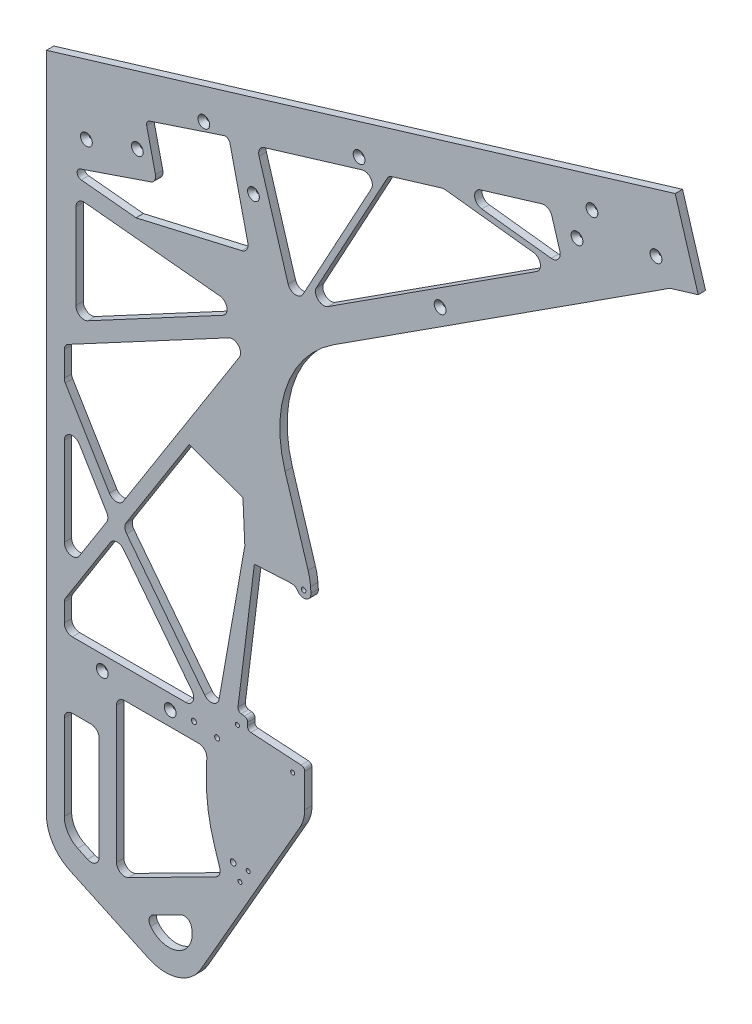
SolidWorks part; units mm, degrees
material "Beech"
ref_plane "Front Plane" through (0, 0, 0) normal (0, 0, 1) x (1, 0, 0)
ref_plane "Top Plane" through (0, 0, 0) normal (0, 1, 0) x (1, 0, 0)
ref_plane "Right Plane" through (0, 0, 0) normal (1, 0, 0) x (0, 0, -1)
sketch "Sketch1" plane through (0, 0, 0) normal (0, 0, 1) x (1, 0, 0)
  line L3 (-17.0528, -329.4943) -> (-52.061, -347.2658)
  line L9 (-123, -235.7894) -> (-123, -309.0696)
  line L10 (-100, -228.7894) -> (-116, -228.7894)
  line L11 (-93, -324.8124) -> (-93, -235.7894)
  line L12 (-111.4524, -327.1958) -> (-102.9583, -331.1566)
  line L20 (84, -200.7842) -> (84, -172.0664)
  line L21 (81.0197, -168.8973) -> (37.7062, -166.2368)
  line L23 (81.0197, -168.8973) -> (37.7062, -166.2368)
  line L24 (89.4313, -36.4853) -> (89.0709, -31.7487)
  line L25 (86.9733, -20.7388) -> (67.1502, 43.2142)
  line L39 (109.0999, 158.659) -> (398.6241, 345.5216)
  line L40 (398.6241, 345.5216) -> (422.935, 352.8794)
  line L46 (422.935, 352.8794) -> (403.0991, 418.4193)
  line L47 (403.0991, 418.4193) -> (-138.3789, 254.5381)
  line L48 (-138.3789, 254.5381) -> (-138.3789, -315.4534)
  line L49 (-118.2139, -347.1062) -> (-50.5059, -378.6789)
  line L50 (-5.4671, -364.4315) -> (80.009, -215.7351)
  line L55 (84, -200.7842) -> (84, -172.0664)
  line L62 (89.4313, -36.4853) -> (89.0709, -31.7487)
  line L63 (86.9733, -20.7388) -> (67.1502, 43.2142)
  line L64 (109.0999, 158.659) -> (398.6241, 345.5216)
  line L65 (398.6241, 345.5216) -> (422.935, 352.8794)
  line L66 (422.935, 352.8794) -> (403.0991, 418.4193)
  line L67 (403.0991, 418.4193) -> (-138.3789, 254.5381)
  line L68 (-138.3789, 254.5381) -> (-138.3789, -315.4534)
  line L69 (-61.1998, 168.1794) -> (29.8266, 189.1945)
  line L70 (-108.3476, 172.8251) -> (-61.1998, 168.1794)
  line L71 (-43.1791, 203.129) -> (-109.2468, 180.5917)
  line L72 (-52.0322, 241.4762) -> (-43.1791, 203.129)
  line L73 (14.4833, 267.3378) -> (-49.3928, 246.173)
  line L74 (35.0726, 197.5898) -> (19.6388, 264.4406)
  line L75 (-102.6958, 70.6213) -> (13.5473, 132.8622)
  line L76 (-113, 150.4873) -> (-113, 76.7923)
  line L77 (10.9295, 145.9995) -> (-105.3136, 157.4535)
  line L78 (-118.2139, -347.1062) -> (-50.5059, -378.6789)
  line L79 (-5.4671, -364.4315) -> (80.009, -215.7351)
  line L81 (-123, -28.6549) -> (-123, -104.7468)
  line L82 (-86.4916, -64.103) -> (-110.0027, -25.0448)
  line L83 (-110.0903, -108.4986) -> (-86.5792, -71.4649)
  line L91 (-78, -203.7894) -> (-78, -320.9929)
  line L92 (-7.2478, -196.7894) -> (-71, -196.7894)
  line L93 (-0.5975, -217.2122) -> (-0.2502, -203.9729)
  line L94 (10.9062, -280.6638) -> (6.4944, -266.8845)
  line L95 (-67.8314, -327.2347) -> (7.4081, -289.0401)
  line L97 (43.2335, -2.4917) -> (44.321, -25.8402) construction
  line L98 (69.3512, -23.7337) -> (62.886, 0.5467) construction
  line L99 (47.5047, -28.6948) -> (66.6392, -27.4998) construction
  line L107 (-15.4708, 21.8839) -> (-69.6883, -63.5168)
  line L108 (30.8453, 5.5646) -> (-15.4708, 21.8839)
  line L109 (32.4846, -29.6329) -> (30.8453, 5.5646)
  line L110 (10.3168, -155.1041) -> (32.4846, -29.6329)
  line L111 (-69.3092, -71.5595) -> (-2.1071, -158.1772)
  line L115 (-83.3585, -85.0495) -> (-123, -147.491)
  line L116 (-12.9629, -160.4984) -> (-71.9182, -84.5103)
  line L117 (-116, -171.7894) -> (-18.4936, -171.7894)
  line L118 (-123, -147.491) -> (-123, -164.7894)
  line L123 (18.5117, 118.5054) -> (-123, 42.7347)
  line L124 (-72.2002, -48.8158) -> (27.7256, 108.5825)
  line L125 (-123, 15.9373) -> (-84.1071, -48.674)
  line L126 (-123, 42.7347) -> (-123, 15.9373)
  line L166 (26.578, -152.854) -> (40.7015, -39.1783)
  line L183 (26.578, -152.854) -> (40.7015, -39.1783)
  line L184 (40.7015, -39.1783) -> (72.3075, -37.5674)
  line L185 (40.7015, -39.1783) -> (72.3075, -37.5674)
  line L240 (34.7318, -162.8731) -> (34.9029, -160.088)
  line L241 (34.7318, -162.8731) -> (34.9029, -160.088)
  line L242 (32.1253, -156.7426) -> (29.3373, -156.3962)
  line L243 (32.1253, -156.7426) -> (29.3373, -156.3962)
  circle A2 centre (83.098, -37.255) radius 2
  arc A4 (-52.061, -347.2658) -> (-17.0528, -329.4943) centre (-32.8243, -341.7931) ccw
  arc A20 (-123, -309.0696) -> (-111.4524, -327.1958) centre (-103, -309.0696) ccw
  arc A21 (-116, -228.7894) -> (-123, -235.7894) centre (-116, -235.7894) ccw
  arc A22 (-93, -235.7894) -> (-100, -228.7894) centre (-100, -235.7894) ccw
  arc A23 (-102.9583, -331.1566) -> (-93, -324.8124) centre (-100, -324.8124) ccw
  arc A31 (89.0709, -31.7487) -> (86.9733, -20.7388) centre (39.215, -35.5422) ccw
  arc A34 (109.0999, 158.659) -> (67.1502, 43.2142) centre (164.1952, 73.2946) ccw
  arc A35 (-138.3789, -315.4534) -> (-118.2139, -347.1062) centre (-103.4539, -315.4534) ccw
  arc A36 (-50.5059, -378.6789) -> (-5.4671, -364.4315) centre (-35.746, -347.0261) ccw
  arc A37 (80.009, -215.7351) -> (84, -200.7842) centre (54, -200.7842) ccw
  arc A46 (29.8266, 189.1945) -> (35.0726, 197.5898) centre (28.252, 196.0151) ccw
  arc A47 (-109.2468, 180.5917) -> (-108.3476, 172.8251) centre (-107.9554, 176.8059) ccw
  arc A48 (-49.3928, 246.173) -> (-52.0322, 241.4762) centre (-48.1347, 242.376) ccw
  arc A49 (19.6388, 264.4406) -> (14.4833, 267.3378) centre (15.7414, 263.5408) ccw
  arc A50 (89.0709, -31.7487) -> (86.9733, -20.7388) centre (39.215, -35.5422) ccw
  arc A51 (109.0999, 158.659) -> (67.1502, 43.2142) centre (164.1952, 73.2946) ccw
  arc A52 (13.5473, 132.8622) -> (10.9295, 145.9995) centre (10.2431, 139.0332) ccw
  arc A53 (-113, 76.7923) -> (-102.6958, 70.6213) centre (-106, 76.7923) ccw
  arc A54 (-105.3136, 157.4535) -> (-113, 150.4873) centre (-106, 150.4873) ccw
  arc A55 (-138.3789, -315.4534) -> (-118.2139, -347.1062) centre (-103.4539, -315.4534) ccw
  arc A56 (-50.5059, -378.6789) -> (-5.4671, -364.4315) centre (-35.746, -347.0261) ccw
  arc A57 (80.009, -215.7351) -> (84, -200.7842) centre (54, -200.7842) ccw
  arc A58 (-110.0027, -25.0448) -> (-123, -28.6549) centre (-116, -28.6549) ccw
  arc A59 (-86.5792, -71.4649) -> (-86.4916, -64.103) centre (-92.4888, -67.7131) ccw
  arc A60 (-123, -104.7468) -> (-110.0903, -108.4986) centre (-116, -104.7468) ccw
  arc A68 (-78, -320.9929) -> (-67.8314, -327.2347) centre (-71, -320.9929) ccw
  arc A69 (-71, -196.7894) -> (-78, -203.7894) centre (-71, -203.7894) ccw
  arc A70 (-0.2502, -203.9729) -> (-7.2478, -196.7894) centre (-7.2478, -203.7894) ccw
  arc A71 (-0.5975, -217.2122) -> (6.4944, -266.8845) centre (149.3509, -221.1459) ccw
  arc A72 (7.4081, -289.0401) -> (10.9062, -280.6638) centre (4.2395, -282.7983) ccw
  arc A74 (44.321, -25.8402) -> (47.5047, -28.6948) centre (47.3177, -25.7007) ccw construction
  arc A75 (62.886, 0.5467) -> (43.2335, -2.4917) centre (53.2227, -2.0264) ccw construction
  arc A76 (66.6392, -27.4998) -> (69.3512, -23.7337) centre (66.4522, -24.5056) ccw construction
  arc A78 (-69.6883, -63.5168) -> (-69.3092, -71.5595) centre (-63.7786, -67.2686) ccw
  arc A79 (-2.1071, -158.1772) -> (10.3168, -155.1041) centre (3.4235, -153.8863) ccw
  arc A84 (-71.9182, -84.5103) -> (-83.3585, -85.0495) centre (-77.4488, -88.8013) ccw
  arc A85 (-18.4936, -171.7894) -> (-12.9629, -160.4984) centre (-18.4936, -164.7894) ccw
  arc A86 (-123, -164.7894) -> (-116, -171.7894) centre (-116, -164.7894) ccw
  arc A88 (27.7256, 108.5825) -> (18.5117, 118.5054) centre (21.8159, 112.3343) ccw
  arc A89 (-84.1071, -48.674) -> (-72.2002, -48.8158) centre (-78.1098, -45.064) ccw
  arc A122 (84, -172.0664) -> (81.0197, -168.8973) centre (80.825, -172.0664) ccw
  arc A123 (84, -172.0664) -> (81.0197, -168.8973) centre (80.825, -172.0664) ccw
  arc A126 (77.9448, -40.4332) -> (83.5751, -43.2993) centre (83.2589, -36.9572) ccw
  arc A127 (77.9448, -40.4332) -> (83.5751, -43.2993) centre (83.2589, -36.9572) ccw
  arc A128 (83.5751, -43.2993) -> (89.4313, -36.4853) centre (83.0996, -36.9671) ccw
  arc A129 (83.5751, -43.2993) -> (89.4313, -36.4853) centre (83.0996, -36.9671) ccw
  arc A136 (77.9448, -40.4332) -> (72.3075, -37.5674) centre (72.6307, -43.9092) ccw
  arc A137 (77.9448, -40.4332) -> (72.3075, -37.5674) centre (72.6307, -43.9092) ccw
  arc A162 (34.7318, -162.8731) -> (37.7062, -166.2368) centre (37.9008, -163.0678) ccw
  arc A163 (34.7318, -162.8731) -> (37.7062, -166.2368) centre (37.9008, -163.0678) ccw
  arc A164 (34.9029, -160.088) -> (32.1253, -156.7426) centre (31.7338, -159.8934) ccw
  arc A165 (34.9029, -160.088) -> (32.1253, -156.7426) centre (31.7338, -159.8934) ccw
  arc A166 (26.578, -152.854) -> (29.3373, -156.3962) centre (29.7288, -153.2454) ccw
  arc A167 (26.578, -152.854) -> (29.3373, -156.3962) centre (29.7288, -153.2454) ccw
  line B0 (236.5506, 323.6498) -> (296.3216, 316.7428)
  line B1 (288.1657, 353.2968) -> (235.3263, 337.3033)
  line B2 (303.8249, 325.7244) -> (296.8934, 348.6248)
  line B3 (104.1239, 184.6459) -> (283.8662, 300.6596)
  line B4 (156.4343, 308.2003) -> (94.1802, 193.8748)
  line B5 (203.4752, 322.4386) -> (156.4343, 308.2003)
  line B6 (280.8737, 313.4946) -> (203.4752, 322.4386)
  line B7 (44.7058, 267.0687) -> (69.7399, 184.3604)
  line B8 (133.2777, 301.1913) -> (49.3777, 275.7965)
  line B9 (82.5874, 183.0407) -> (141.4532, 291.1438)
  arc B10 (296.3216, 316.7428) -> (303.8249, 325.7244) centre (297.1251, 323.6965) ccw
  arc B11 (235.3263, 337.3033) -> (236.5506, 323.6498) centre (237.3542, 330.6035) ccw
  arc B12 (296.8934, 348.6248) -> (288.1657, 353.2968) centre (290.1936, 346.5969) ccw
  arc B13 (283.8662, 300.6596) -> (280.8737, 313.4946) centre (280.0701, 306.5409) ccw
  arc B14 (94.1802, 193.8748) -> (104.1239, 184.6459) centre (100.3278, 190.5272) ccw
  arc B15 (69.7399, 184.3604) -> (82.5874, 183.0407) centre (76.4398, 186.3883) ccw
  arc B16 (49.3777, 275.7965) -> (44.7058, 267.0687) centre (51.4056, 269.0966) ccw
  arc B17 (141.4532, 291.1438) -> (133.2777, 301.1913) centre (135.3056, 294.4914) ccw
  dimension "D1" = 0
sketch_block_instance "Block1-1"
sketch_block "Block1"
extrude "Boss-Extrude1" add sketch "Sketch1" along normal blind 6.35
hole_wizard "#8 Clearance Hole1" positions "Sketch2" profile "Sketch3" hole size "#8" standard "ANSI Inch" end condition through all
sketch "Sketch2" plane through (0, 0, 6.35) normal (0, 0, 1) x (1, 0, 0)
  point P0 (22.4173, -270.7692)
sketch "Sketch3" plane through (22.4173, -270.7692, 6.35) normal (1, 0, 0) x (0, -1, 0)
  line L0 (0, 0) -> (0, 6.35)
  line L1 (0, 6.35) -> (2.4574, 6.35)
  line L2 (2.4574, 6.35) -> (2.4574, 0)
  line L5 (2.4574, 0) -> (0, 0)
  line L11 (0, -6.35) -> (0, 107.95) construction
  dimension "Thru Hole Dia." = 4.9149
  dimension "Thru Hole Depth" = 6.35
hole_wizard "#29 (0.136) Diameter Hole1" positions "Sketch4" profile "Sketch5" hole size "#29" standard "ANSI Inch" end condition through all
sketch "Sketch4" plane through (0, 0, 6.35) normal (0, 0, 1) x (1, 0, 0)
  point P0 (28.3036, -282.3356)
  point P5 (35.3953, -270.7692)
  point P9 (26.0849, -166.3788)
  point P12 (73.6862, -178.0913)
sketch "Sketch5" plane through (28.3036, -282.3356, 6.35) normal (1, 0, 0) x (0, -1, 0)
  line L0 (0, 0) -> (0, 6.35)
  line L1 (0, 6.35) -> (1.7272, 6.35)
  line L2 (1.7272, 6.35) -> (1.7272, 0)
  line L5 (1.7272, 0) -> (0, 0)
  line L11 (0, -6.35) -> (0, 107.95) construction
  dimension "Thru Hole Dia." = 3.4544
  dimension "Thru Hole Depth" = 6.35
fillet "Fillet2" radius 6.35 8 edges at (-52.061, -347.2658, 3.175) (-17.0528, -329.4943, 3.175) (-123, -147.491, 3.175) (-123, 15.9373, 3.175) (-123, 42.7347, 3.175) (-43.1791, 203.129, 3.175) (156.4343, 308.2003, 3.175) (203.4752, 322.4386, 3.175)
hole_wizard "Hole1" positions "Sketch6" profile "Sketch7" legacy
sketch "Sketch6" plane through (-277.2867, -215.2871, 6.35) normal (0, 0, 1) x (-0.09, -0.9959, 0)
  point P4 (-507.0387, 229.7761)
  point P6 (-559.3712, 359.3037)
  point P8 (-637.87, 553.5951)
  point P10 (-636.0712, 609.1114)
  point P12 (-609.4494, 543.2202)
  point P14 (-488.8705, 435.7568)
  point P16 (-478.4144, 275.2927)
  point P18 (-453.1036, 177.1887)
  point P20 (-434.4591, 134.8062)
  point P22 (-52.9605, 241.7526)
  point P24 (-47.6978, 183.4898)
sketch "Sketch7" plane through (-2.8292, 269.0251, 6.35) normal (1, 0, 0) x (0, -1, 0)
  line L0 (0, 0) -> (0, 32.7039)
  line L1 (0, 32.7039) -> (1.5875, 31.75)
  line L2 (1.5875, 31.75) -> (1.5875, 4.0177)
  line L3 (1.5875, 4.0177) -> (5.08, 0)
  line L4 (5.08, 0) -> (0, 0)
  line L5 (0, -14.3089) -> (0, 102.4216) construction
  line L6 (0, 32.7039) -> (-1.5875, 31.75) construction
  line L7 (-1.5875, 4.0177) -> (-5.08, 0) construction
  dimension "Diameter" = 3.175
  dimension "Depth" = 31.75
  dimension "C-Sink Diameter" = 10.16
  dimension "C-Sink Angle" = 82
  dimension "Drill Angle" = 118
hole_wizard "#6 Clearance Hole1" positions "Sketch8" profile "Sketch9" hole size "#6" standard "ANSI Inch" end condition up to next
sketch "Sketch8" plane through (0, 0, 6.35) normal (0, 0, 1) x (1, 0, 0)
  point P0 (8.6038, -184.7304)
  point P2 (-11.3597, -182.482)
sketch "Sketch9" plane through (8.6038, -184.7304, 6.35) normal (1, 0, 0) x (0, -1, 0)
  line L0 (0, 0) -> (0, 6.35)
  line L1 (0, 6.35) -> (2.1526, 6.35)
  line L2 (2.1526, 6.35) -> (2.1526, 0)
  line L5 (2.1526, 0) -> (0, 0)
  line L11 (0, -6.35) -> (0, 107.95) construction
  dimension "Thru Hole Dia." = 4.3053
  dimension "Thru Hole Depth" = 6.35
